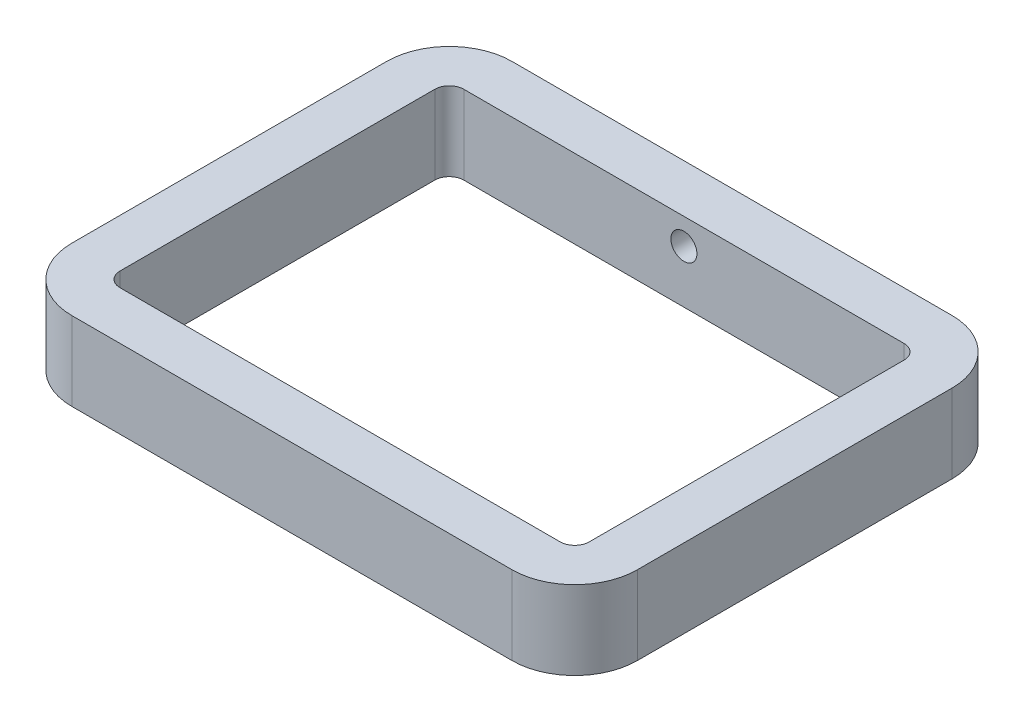
SolidWorks part; units mm, degrees
ref_plane "Front Plane" through (0, 0, 0) normal (0, 0, 1) x (1, 0, 0)
ref_plane "Top Plane" through (0, 0, 0) normal (0, 1, 0) x (1, 0, 0)
ref_plane "Right Plane" through (0, 0, 0) normal (1, 0, 0) x (0, 0, -1)
sketch "Sketch1" plane through (0, 0, 0) normal (0, 1, 0) x (1, 0, 0)
  line L0 (-47.5, -7.5125) -> (-47.5, -71.5125)
  line L1 (-44.75, -4.7625) -> (44.75, -4.7625)
  line L2 (47.5, -7.5125) -> (47.5, -71.5125)
  line L3 (-44.75, -74.2625) -> (44.75, -74.2625)
  line L4 (-44.75, 5.2375) -> (44.75, 5.2375)
  line L5 (57.5, -7.5125) -> (57.5, -71.5125)
  line L6 (-44.75, -84.2625) -> (44.75, -84.2625)
  line L7 (-57.5, -7.5125) -> (-57.5, -71.5125)
  arc A0 (-47.5, -71.5125) -> (-44.75, -74.2625) centre (-44.75, -71.5125) ccw construction
  arc A1 (44.75, -74.2625) -> (47.5, -71.5125) centre (44.75, -71.5125) ccw construction
  arc A2 (47.5, -7.5125) -> (44.75, -4.7625) centre (44.75, -7.5125) ccw construction
  arc A3 (-44.75, -4.7625) -> (-47.5, -7.5125) centre (-44.75, -7.5125) ccw construction
  arc A4 (-47.5, -71.5125) -> (-44.75, -74.2625) centre (-44.75, -71.5125) ccw
  arc A5 (44.75, -74.2625) -> (47.5, -71.5125) centre (44.75, -71.5125) ccw
  arc A6 (47.5, -7.5125) -> (44.75, -4.7625) centre (44.75, -7.5125) ccw
  arc A7 (-44.75, -4.7625) -> (-47.5, -7.5125) centre (-44.75, -7.5125) ccw
  arc A8 (57.5, -7.5125) -> (44.75, 5.2375) centre (44.75, -7.5125) ccw
  arc A9 (44.75, -84.2625) -> (57.5, -71.5125) centre (44.75, -71.5125) ccw
  arc A10 (-57.5, -71.5125) -> (-44.75, -84.2625) centre (-44.75, -71.5125) ccw
  arc A11 (-44.75, 5.2375) -> (-57.5, -7.5125) centre (-44.75, -7.5125) ccw
  dimension "D1" = 10
extrude "Boss-Extrude1" add sketch "Sketch1" along normal blind 16
sketch "Sketch2" plane through (0, 0, 4.7625) normal (0, 0, 1) x (1, 0, 0)
  circle A0 centre (0, 10.7219) radius 2.65
  dimension "D1" = 5.3
extrude "Cut-Extrude1" cut sketch "Sketch2" against normal blind 20
sketch "Sketch3" plane through (0, 0, 0) normal (0, 1, 0) x (1, 0, 0)
  line L0 (44.75, -4.7625) -> (-44.75, -4.7625) construction
  line L1 (-44.75, -74.2625) -> (44.75, -74.2625) construction
  line L2 (47.5, -71.5125) -> (47.5, -7.5125) construction
  line L3 (-47.5, -7.5125) -> (-47.5, -71.5125) construction
  line L4 (-44.75, -74.2625) -> (44.75, -74.2625)
  line L5 (47.5, -71.5125) -> (47.5, -7.5125)
  line L6 (-47.5, -7.5125) -> (-47.5, -71.5125)
  line L7 (44.75, -4.7625) -> (-44.75, -4.7625)
  line L12 (-47.7, -7.5125) -> (-47.7, -71.5125)
  line L13 (-44.75, -74.4625) -> (44.75, -74.4625)
  line L14 (47.7, -71.5125) -> (47.7, -7.5125)
  line L15 (44.75, -4.5625) -> (-44.75, -4.5625)
  arc A0 (-47.5, -71.5125) -> (-44.75, -74.2625) centre (-44.75, -71.5125) ccw construction
  arc A1 (44.75, -74.2625) -> (47.5, -71.5125) centre (44.75, -71.5125) ccw construction
  arc A2 (47.5, -7.5125) -> (44.75, -4.7625) centre (44.75, -7.5125) ccw construction
  arc A3 (-44.75, -4.7625) -> (-47.5, -7.5125) centre (-44.75, -7.5125) ccw construction
  arc A4 (-47.5, -71.5125) -> (-44.75, -74.2625) centre (-44.75, -71.5125) ccw
  arc A5 (44.75, -74.2625) -> (47.5, -71.5125) centre (44.75, -71.5125) ccw
  arc A6 (47.5, -7.5125) -> (44.75, -4.7625) centre (44.75, -7.5125) ccw
  arc A7 (-44.75, -4.7625) -> (-47.5, -7.5125) centre (-44.75, -7.5125) ccw
  arc A12 (-44.75, -4.5625) -> (-47.7, -7.5125) centre (-44.75, -7.5125) ccw
  arc A13 (-47.7, -71.5125) -> (-44.75, -74.4625) centre (-44.75, -71.5125) ccw
  arc A14 (44.75, -74.4625) -> (47.7, -71.5125) centre (44.75, -71.5125) ccw
  arc A15 (47.7, -7.5125) -> (44.75, -4.5625) centre (44.75, -7.5125) ccw
  dimension "D1" = 0.2
extrude "Cut-Extrude2" cut sketch "Sketch3" against normal through all both and the other way through all
